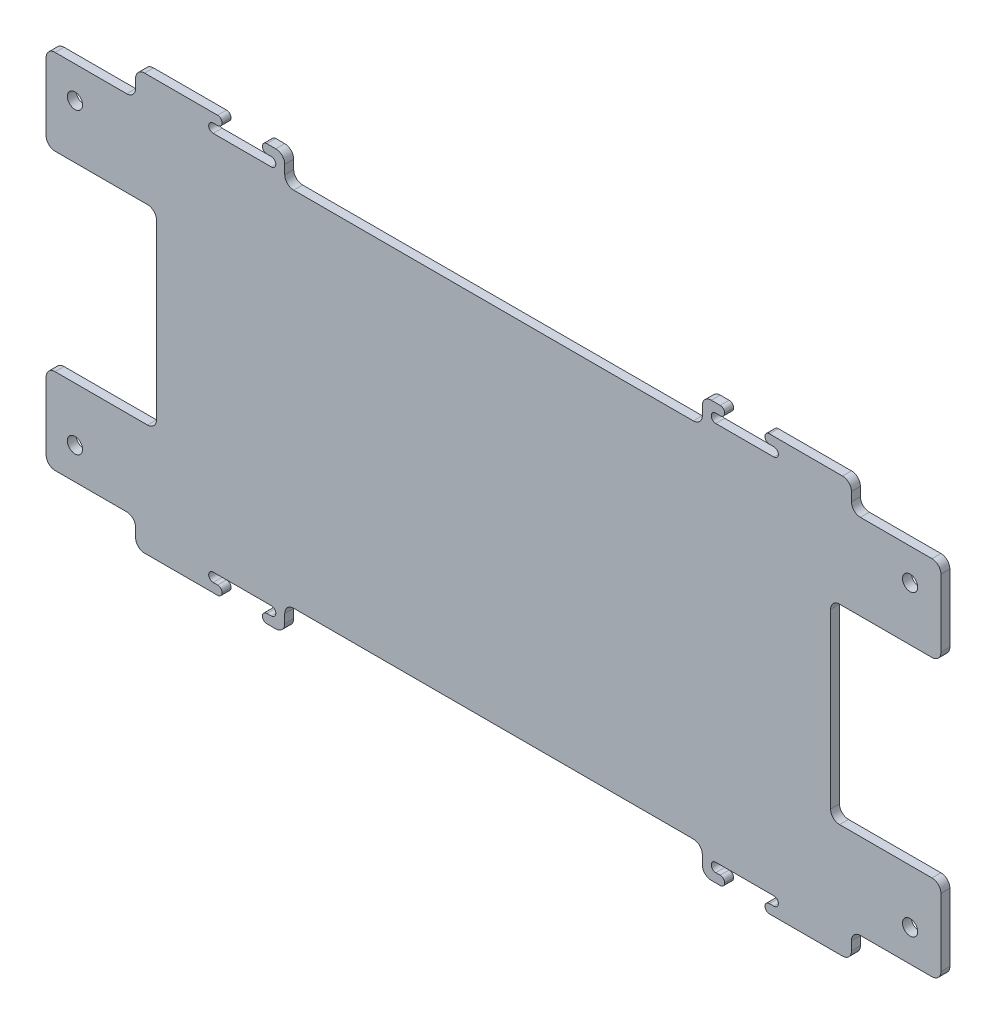
SolidWorks part; units mm, degrees
ref_plane "Front Plane" through (0, 0, 0) normal (0, 0, 1) x (1, 0, 0)
ref_plane "Top Plane" through (0, 0, 0) normal (0, 1, 0) x (1, 0, 0)
ref_plane "Right Plane" through (0, 0, 0) normal (1, 0, 0) x (0, 0, -1)
sketch "Sketch1" plane through (0, 0, 0) normal (0, 0, 1) x (1, 0, 0)
  line L0 (178.3692, 60.7015) -> (-178.3692, 60.7015) construction
  line L1 (-150, -60.7015) -> (150, -60.7015)
  line L2 (-150, -60.7015) -> (-150, 60.7015)
  line L3 (-150, 60.7015) -> (150, 60.7015)
  line L4 (150, -60.7015) -> (150, 60.7015)
  line L5 (-150, -60.7015) -> (150, 60.7015) construction
  line L6 (-150, 60.7015) -> (150, -60.7015) construction
  point P0 (0, 0)
  dimension "D1" = 300
extrude "Boss-Extrude1" add sketch "Sketch1" along normal blind 3 contours L3 L4 L1 L2
sketch "Sketch2" plane through (0, 0, 3) normal (0, 0, 1) x (1, 0, 0)
  line L0 (-125, 30) -> (-175, 30) construction
  line L1 (-164.146, -32) -> (-113, -32)
  line L2 (-164.146, -32) -> (-164.146, 32)
  line L3 (-164.146, 32) -> (-113, 32)
  line L4 (-113, -32) -> (-113, 32)
  line L5 (-164.146, -32) -> (-113, 32) construction
  line L6 (-164.146, 32) -> (-113, -32) construction
  line L7 (-115, -20) -> (-115, 20) construction
  point P0 (-138.573, 0)
  dimension "D1" = 2
  dimension "D3" = 2
extrude "Cut-Extrude1" cut sketch "Sketch2" against normal up to surface (3 mm away) up to face at (0, 0, 0)
mirror "Mirror1" about plane through (0, 0, 0) normal (1, 0, 0) of "Cut-Extrude1"
sketch "Sketch3" plane through (0, 0, 3) normal (0, 0, 1) x (1, 0, 0)
  line L0 (-150, -60.7015) -> (150, -60.7015) construction
  line L1 (-120, -60.7015) -> (-70, -60.7015)
  line L2 (-120, -60.7015) -> (-120, -69.7015)
  line L3 (-120, -69.7015) -> (-70, -69.7015)
  line L4 (-70, -60.7015) -> (-70, -69.7015)
  line L5 (-94, -65.2015) -> (-74.5, -65.2015) construction
  line L6 (-94, -63.7015) -> (-74.5, -63.7015)
  line L7 (-94, -66.7015) -> (-74.5, -66.7015)
  arc A0 (-94, -63.7015) -> (-94, -66.7015) centre (-94, -65.2015) ccw
  arc A1 (-74.5, -66.7015) -> (-74.5, -63.7015) centre (-74.5, -65.2015) ccw
  point P8 (-84.25, -65.2015)
  point P17 (-120, -65.2015)
  dimension "D3" = 70
  dimension "D4" = 4.5
  dimension "D1" = 50
  dimension "D2" = 9
extrude "Boss-Extrude2" add sketch "Sketch3" against normal up to surface (3 mm away) up to face at (0, 0, 0)
mirror "Mirror3" about plane through (0, 0, 0) normal (0, 1, 0) of "Boss-Extrude2"
mirror "Mirror4" about plane through (0, 0, 0) normal (1, 0, 0) of "Mirror3", "Boss-Extrude2"
fillet "Fillet2" radius 3 16 edges at (-120, 60.7015, 1.5) (-120, 69.7015, 1.5) (-70, 69.7015, 1.5) (-70, 60.7015, 1.5) (70, 60.7015, 1.5) (70, 69.7015, 1.5) (120, 60.7015, 1.5) (120, 69.7015, 1.5) (70, -69.7015, 1.5) (70, -60.7015, 1.5) (120, -69.7015, 1.5) (120, -60.7015, 1.5) (-70, -69.7015, 1.5) (-70, -60.7015, 1.5) (-120, -69.7015, 1.5) (-120, -60.7015, 1.5)
fillet "Fillet3" radius 3 12 edges at (-113, -32, 1.5) (-150, 60.7015, 1.5) (-113, 32, 1.5) (-150, 32, 1.5) (-150, -60.7015, 1.5) (-150, -32, 1.5) (150, 60.7015, 1.5) (150, 32, 1.5) (113, 32, 1.5) (150, -32, 1.5) (113, -32, 1.5) (150, -60.7015, 1.5)
sketch "Sketch4" plane through (0, 0, 0) normal (0, 0, -1) x (-1, 0, 0)
  circle A0 centre (-139.6609, -50) radius 2.55
  circle A1 centre (-139.6609, 50) radius 2.55
  circle A2 centre (140.3391, -50) radius 2.55
  circle A3 centre (140.3391, 50) radius 2.55
  dimension "D1" = 5.1
  dimension "D2" = 5.1
  dimension "D3" = 5.1
  dimension "D4" = 5.1
extrude "Cut-Extrude2" cut sketch "Sketch4" against normal up to surface (3 mm away) up to face at (0, 0, 3)
sketch "Sketch5" plane through (0, 0, 3) normal (0, 0, 1) x (1, 0, 0)
  line L0 (117, 69.7015) -> (73, 69.7015) construction
  line L1 (77.5, 69.7015) -> (91, 69.7015)
  line L2 (77.5, 69.7015) -> (77.5, 66.7015)
  line L3 (77.5, 66.7015) -> (91, 66.7015)
  line L4 (91, 69.7015) -> (91, 66.7015)
  line L5 (94, 66.7015) -> (74.5, 66.7015) construction
  dimension "D1" = 3
  dimension "D2" = 3
extrude "Cut-Extrude3" cut sketch "Sketch5" against normal up to surface (3 mm away) up to face at (137.1109, 50, 0)
mirror "Mirror5" about plane through (0, 0, 0) normal (0, 1, 0) of "Cut-Extrude3"
mirror "Mirror6" about plane through (0, 0, 0) normal (1, 0, 0) of "Mirror5", "Cut-Extrude3"
fillet "Fillet4" radius 1.5 16 edges at (91, 66.7015, 1.5) (77.5, 66.7015, 1.5) (77.5, 69.7015, 1.5) (91, 69.7015, 1.5) (-91, 69.7015, 1.5) (-91, 66.7015, 1.5) (-77.5, 66.7015, 1.5) (-77.5, 69.7015, 1.5) (-77.5, -69.7015, 1.5) (-77.5, -66.7015, 1.5) (-91, -69.7015, 1.5) (-91, -66.7015, 1.5) (77.5, -69.7015, 1.5) (91, -69.7015, 1.5) (91, -66.7015, 1.5) (77.5, -66.7015, 1.5)
